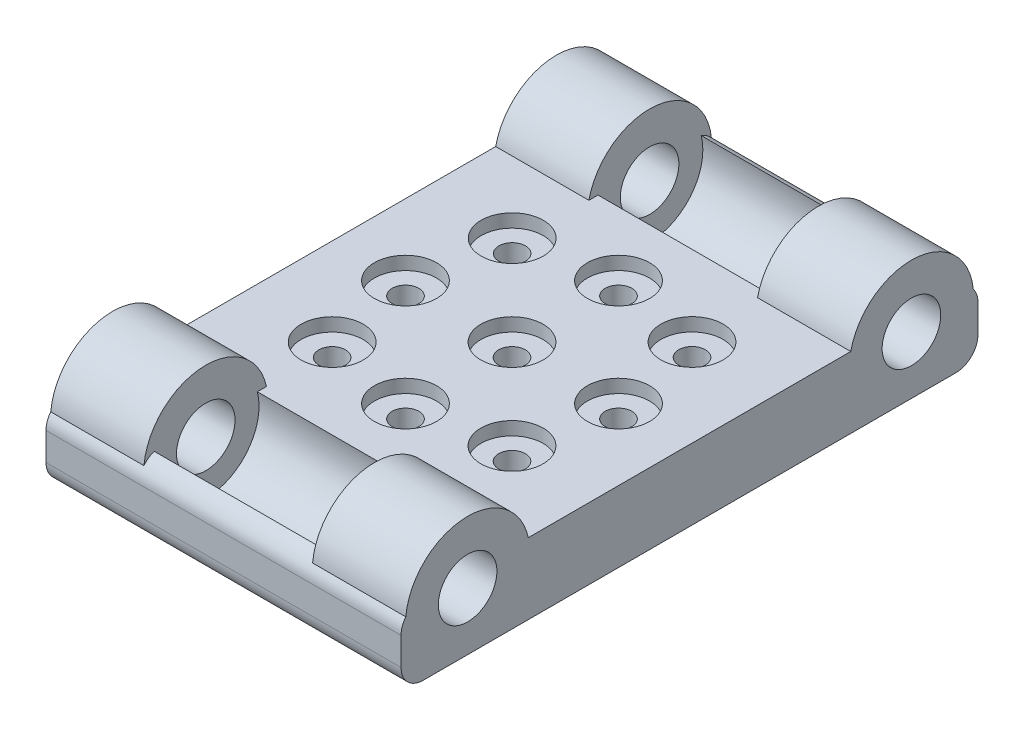
SolidWorks part; units mm, degrees
ref_plane "Front Plane" through (0, 0, 0) normal (0, 0, 1) x (1, 0, 0)
ref_plane "Top Plane" through (0, 0, 0) normal (0, 1, 0) x (1, 0, 0)
ref_plane "Right Plane" through (0, 0, 0) normal (1, 0, 0) x (0, 0, -1)
sketch "草图1" plane through (0, 0, 0) normal (0, 1, 0) x (1, 0, 0)
  line L1 (-21.4672, 26.4865) -> (18.5328, 26.4865)
  line L2 (-21.4672, 26.4865) -> (-21.4672, -38.5135)
  line L3 (-21.4672, -38.5135) -> (18.5328, -38.5135)
  line L4 (18.5328, 26.4865) -> (18.5328, -38.5135)
  dimension "D1" = 40
  dimension "D2" = 65
extrude "凸台-拉伸1" add sketch "草图1" along normal blind 8
sketch "草图5" plane through (18.5328, 0, 0) normal (1, 0, 0) x (0, 0, -1)
  line L3 (26.4865, 8) -> (26.4865, 0) construction
  line L5 (-38.5135, 0) -> (26.4865, 0) construction
  circle A2 centre (18.9865, 6.5) radius 6
  circle A3 centre (-31.0135, 6.5) radius 6
  dimension "D1" = 7.5
  dimension "D2" = 50
  dimension "D3" = 12
  dimension "D4" = 12
  dimension "D6" = 6.5
extrude "切除-拉伸2" cut sketch "草图5" against normal blind 44
sketch "草图6" plane through (18.5328, 0, 0) normal (1, 0, 0) x (0, 0, -1)
  line L0 (22.9632, 0) -> (14.3247, 0)
  line L1 (-38.5135, 0) -> (26.4865, 0) construction
  line L2 (14.3247, 0) -> (-31.3346, 0)
  circle A0 centre (18.9865, 6.5) radius 3.3
  circle A1 centre (18.9865, 6.5) radius 7
  circle A2 centre (-31.0135, 6.5) radius 3.3
  circle A3 centre (-31.0135, 6.5) radius 7
  line M3 (26.4865, 8) -> (24.796, 8)
  arc M4 (24.796, 8) -> (13.177, 8) centre (18.9865, 6.5) cw
  line M5 (13.177, 8) -> (-25.204, 8)
  arc M6 (-25.204, 8) -> (-36.823, 8) centre (-31.0135, 6.5) cw
  line M7 (-36.823, 8) -> (-38.5135, 8)
  dimension "D1" = 14
  dimension "D2" = 14
  dimension "D3" = 6.6
  dimension "D4" = 6.6
extrude "凸台-拉伸2" add sketch "草图6" against normal blind 10.5 contours A1 L0 M5 M3 M4 | A1 A0 M3 M5 M4 | A3 A2 M5 M7 M6 | A3 L2 M7 M5 M6
sketch "草图7" plane through (-21.4672, 0, 0) normal (-1, 0, 0) x (0, 0, 1)
  line L0 (38.5135, 0) -> (-26.4865, 0)
  circle A0 centre (31.0135, 6.5) radius 3.3
  circle A1 centre (31.0135, 6.5) radius 7
  circle A2 centre (-18.9865, 6.5) radius 3.3
  circle A3 centre (-18.9865, 6.5) radius 6
  circle A4 centre (-18.9865, 6.5) radius 7
  line M1 (25.204, 8) -> (-13.177, 8)
  arc M2 (-13.177, 8) -> (-24.796, 8) centre (-18.9865, 6.5) cw
  line M3 (-24.796, 8) -> (-26.4865, 8)
  line M7 (38.5135, 8) -> (36.823, 8)
  arc M8 (36.823, 8) -> (25.204, 8) centre (31.0135, 6.5) cw
  dimension "D1" = 14
  dimension "D2" = 6.6
  dimension "D3" = 6.6
extrude "凸台-拉伸3" add sketch "草图7" against normal blind 10.5 contours A1 A0 M7 M1 M8 | A1 L0 M1 M7 M8 | A4 L0 M3 M1 M2 | A3 A2 M2 | A4 A3 M1 M3
sketch "草图8" plane through (0, 0, 0) normal (0, -1, 0) x (1, 0, 0)
  line L0 (-21.4672, -26.4865) -> (-21.4672, 38.5135) construction
  line L1 (18.5328, -26.4865) -> (-21.4672, -26.4865) construction
  circle A0 centre (-1.4672, 6.0135) radius 1.5
  circle A1 centre (-13.4672, 6.0135) radius 1.5
  circle A2 centre (-1.4672, 18.0135) radius 1.5
  circle A3 centre (10.5328, 6.0135) radius 1.5
  circle A4 centre (-1.4672, -5.9865) radius 1.5
  dimension "D1" = 3
  dimension "D2" = 3
  dimension "D3" = 3
  dimension "D4" = 3
  dimension "D5" = 3
  dimension "D6" = 12
  dimension "D7" = 12
  dimension "D8" = 12
  dimension "D9" = 12
  dimension "D10" = 0
  dimension "D11" = 20
  dimension "D12" = 32.5
extrude "切除-拉伸3" cut sketch "草图8" against normal blind 10.5
fillet "圆角1" radius 2.5 4 edges at (-1.4672, 8, 38.5135) (-1.4672, 8, -26.4865) (-1.4672, 0, -26.4865) (-1.4672, 0, 38.5135)
sketch "草图10" plane through (0, 0, 0) normal (0, -1, 0) x (-1, 0, 0)
  line L1 (21.4672, -38.5135) -> (-18.5328, -38.5135) construction
  line L2 (-18.5328, -36.0135) -> (-18.5328, 23.9865) construction
  circle A0 centre (-8.6628, 4.1365) radius 3
  circle A1 centre (11.5972, 4.1365) radius 3
  circle A2 centre (-8.6628, -16.1435) radius 3
  circle A3 centre (11.5972, -16.1435) radius 3
  dimension "D1" = 6
  dimension "D2" = 6
  dimension "D3" = 6
  dimension "D4" = 6
  dimension "D5" = 20.28
  dimension "D6" = 22.37
  dimension "D7" = 22.37
  dimension "D9" = 20.26
  dimension "D10" = 9.87
  dimension "D11" = 20.26
  dimension "D12" = 9.87
extrude "凸台-拉伸4" add sketch "草图10" along normal blind 1
chamfer "倒角1" distance 1.5 distance2 0.5 4 edges at (8.6628, -1, 13.1435) (8.6628, -1, -7.1365) (-11.5972, -1, 13.1435) (-11.5972, -1, -7.1365)
sketch "草图11" plane through (0, -1, 0) normal (0, -1, 0) x (1, 0, 0)
  circle A0 centre (-11.5972, -4.1365) radius 1.5
  circle A1 centre (-11.5972, 16.1435) radius 1.5
  circle A2 centre (8.6628, 16.1435) radius 1.5
  circle A3 centre (8.6628, -4.1365) radius 1.5
  dimension "D1" = 3
  dimension "D2" = 3
  dimension "D3" = 3
  dimension "D4" = 3
extrude "切除-拉伸4" cut sketch "草图11" against normal blind 22.5
sketch "草图12" plane through (0, 8, 0) normal (0, 1, 0) x (1, 0, 0)
  circle A0 centre (8.6628, 4.1365) radius 3.5
  circle A1 centre (10.5328, -6.0135) radius 3.5
  circle A2 centre (8.6628, -16.1435) radius 3.5
  circle A3 centre (-1.4672, 5.9865) radius 3.5
  circle A4 centre (-1.4672, -6.0135) radius 3.5
  circle A5 centre (-1.4672, -18.0135) radius 3.5
  circle A6 centre (-11.5972, -16.1435) radius 3.5
  circle A7 centre (-13.4672, -6.0135) radius 3.5
  circle A8 centre (-11.5972, 4.1365) radius 3.5
  dimension "D1" = 7
  dimension "D2" = 7
  dimension "D3" = 7
  dimension "D4" = 7
  dimension "D5" = 7
  dimension "D6" = 7
  dimension "D7" = 7
  dimension "D8" = 7
  dimension "D9" = 7
extrude "切除-拉伸5" cut sketch "草图12" against normal blind 1.5
equation "\"2.5.00mm\"=10"
